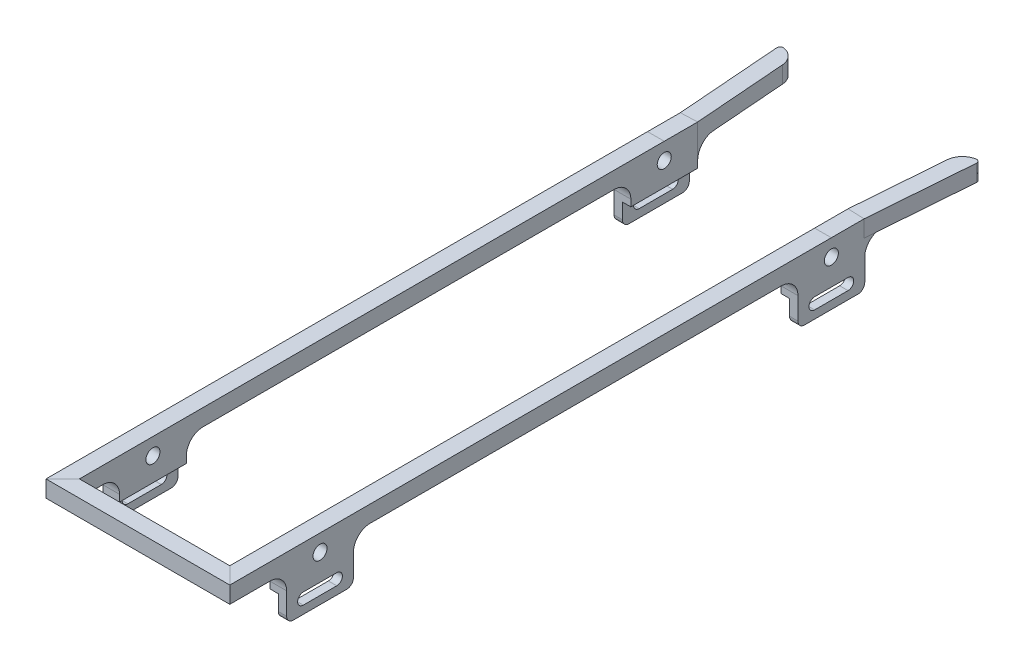
SolidWorks part; units mm, degrees
ref_plane "Front Plane" through (0, 0, 0) normal (0, 0, 1) x (1, 0, 0)
ref_plane "Top Plane" through (0, 0, 0) normal (0, 1, 0) x (1, 0, 0)
ref_plane "Right Plane" through (0, 0, 0) normal (1, 0, 0) x (0, 0, -1)
sketch "rail_path" plane through (0, 0, 0) normal (0, 1, 0) x (1, 0, 0)
  line L0 (28.575, 111.125) -> (28.575, 123.825)
  line L1 (-28.575, -111.125) -> (28.575, -111.125)
  line L2 (-28.575, -111.125) -> (-28.575, 111.125)
  line L3 (-28.575, 111.125) -> (28.575, 111.125) construction
  line L4 (28.575, -111.125) -> (28.575, 111.125)
  line L5 (-28.575, -111.125) -> (28.575, 111.125) construction
  line L6 (-28.575, 111.125) -> (28.575, -111.125) construction
  line L7 (-28.575, 111.125) -> (-28.575, 123.825)
  line L8 (28.575, 123.825) -> (31.75, 165.1)
  line L9 (-28.575, 123.825) -> (-31.75, 165.1)
  point P0 (0, 0)
  dimension "D1" = 222.25
  dimension "D2" = 57.15
  dimension "D3" = 12.7
  dimension "D4" = 12.7
  dimension "D5" = 41.275
  dimension "D6" = 3.175
  dimension "D7" = 3.175
sketch "rail_profile" plane through (0, 0, 0) normal (0, 0, 1) x (1, 0, 0)
  line L0 (-28.575, 0) -> (28.575, 0) construction
  line L1 (28.575, 0) -> (34.925, 0)
  line L2 (28.575, 0) -> (28.575, 6.35)
  line L3 (28.575, 6.35) -> (34.925, 6.35)
  line L4 (34.925, 0) -> (34.925, 6.35)
  line L5 (-28.575, 0) -> (28.575, 0) construction
  dimension "D1" = 6.35
  dimension "D2" = 6.35
sweep "Sweep1" add profiles "rail_profile" path "rail_path"
sketch "clip_profile" plane through (0, 0, 0) normal (0, 0, 1) x (1, 0, 0)
  line L4 (28.575, 0) -> (-28.575, 0)
  line L12 (-28.575, 6.35) -> (28.575, 6.35)
  line L34 (34.925, -17.272) -> (31.75, -17.272)
  line L38 (28.575, -8.89) -> (31.75, -8.89)
  line L39 (31.75, -17.272) -> (31.75, -8.89)
  line L47 (31.75, 6.35) -> (38.0813, 6.35)
  line L48 (34.925, -17.272) -> (34.925, -8.89)
  line L49 (38.0813, 6.35) -> (38.0813, 0)
  line L50 (28.575, -8.89) -> (34.925, -8.89)
  line L51 (28.575, -8.89) -> (28.575, 0)
  line L52 (28.575, 0) -> (34.925, 0)
  line L53 (34.925, -8.89) -> (34.925, 0)
  line L54 (31.75, 6.35) -> (38.0813, 6.35)
  line L55 (38.0813, 6.35) -> (38.0813, 0)
  line L56 (38.0813, 0) -> (31.75, 0)
  line L57 (31.75, 0) -> (28.575, 0)
  line L58 (38.0813, 0) -> (31.75, 0)
  line L59 (-28.575, 0) -> (-31.75, 0)
  line L60 (-31.75, 0) -> (-38.0813, 0)
  line L61 (-38.0813, 0) -> (-38.0813, 6.35)
  line L62 (-38.0813, 6.35) -> (-31.75, 6.35)
  line L63 (-31.75, 6.35) -> (-28.575, 6.35)
  line L64 (31.75, 0) -> (28.575, 0)
  line L65 (28.575, 6.35) -> (31.75, 6.35)
  line L66 (-28.575, 0) -> (-31.75, 0)
  line L67 (-31.75, 0) -> (-38.0813, 0)
  line L68 (-38.0813, 0) -> (-38.0813, 6.35)
  line L69 (-38.0813, 6.35) -> (-31.75, 6.35)
  line L70 (-31.75, 6.35) -> (-28.575, 6.35)
  line L71 (28.575, 6.35) -> (31.75, 6.35)
  dimension "D1" = 8.89
  dimension "D2" = 3.175
  dimension "D4" = 8.382
ref_plane "BackClipPlane" through (0, 0, 83.185) normal (0, 0, -1) x (-1, 0, 0)
ref_plane "FrontClipPlane" through (0, 0, -111.125) normal (0, 0, -1) x (-1, 0, 0)
sketch "BackClipProfile" plane through (0, 0, 83.185) normal (0, 0, -1) x (-1, 0, 0)
  line L24 (-34.925, -8.89) -> (-34.925, 0) construction
  line L25 (-34.925, -17.272) -> (-34.925, -8.89) construction
  line L26 (-34.925, -17.272) -> (-31.75, -17.272) construction
  line L27 (-31.75, -17.272) -> (-31.75, -8.89) construction
  line L28 (-28.575, -8.89) -> (-31.75, -8.89) construction
  line L29 (-28.575, -8.89) -> (-28.575, 0) construction
  line L30 (-34.925, -8.89) -> (-34.925, 0)
  line L31 (-34.925, -17.272) -> (-34.925, -8.89)
  line L32 (-34.925, -17.272) -> (-31.75, -17.272)
  line L33 (-31.75, -17.272) -> (-31.75, -8.89)
  line L34 (-28.575, -8.89) -> (-31.75, -8.89)
  line L35 (-28.575, -8.89) -> (-28.575, 0)
  line L36 (-28.575, 0) -> (-34.925, 0)
sketch "FrontClipProfile" plane through (0, 0, -111.125) normal (0, 0, -1) x (-1, 0, 0)
  line L24 (-31.75, -17.272) -> (-31.75, -8.89) construction
  line L25 (-34.925, -17.272) -> (-31.75, -17.272) construction
  line L26 (-34.925, -17.272) -> (-34.925, -8.89) construction
  line L27 (-34.925, -8.89) -> (-34.925, 0) construction
  line L28 (-28.575, -8.89) -> (-31.75, -8.89) construction
  line L29 (-28.575, -8.89) -> (-28.575, 0) construction
  line L30 (-31.75, -17.272) -> (-31.75, -8.89)
  line L31 (-34.925, -17.272) -> (-31.75, -17.272)
  line L32 (-34.925, -17.272) -> (-34.925, -8.89)
  line L33 (-34.925, -8.89) -> (-34.925, 0)
  line L34 (-28.575, -8.89) -> (-31.75, -8.89)
  line L35 (-28.575, -8.89) -> (-28.575, 0)
  line L36 (-28.575, 0) -> (-34.925, 0)
extrude "BackClip" add sketch "BackClipProfile" along normal mid plane 25.4
mirror "BackClipMirror" about plane through (0, 0, 0) normal (1, 0, 0) of "BackClip"
extrude "FrontClip" add sketch "FrontClipProfile" along normal mid plane 25.4
mirror "FrontClipMirror" about plane through (0, 0, 0) normal (1, 0, 0) of "FrontClip"
sketch "Sketch8" plane through (28.575, 0, 0) normal (-1, 0, 0) x (0, 0, 1)
  line L0 (83.185, 3.4925) -> (83.185, -3.4925) construction
  line L9 (111.125, 6.35) -> (-111.125, 6.35) construction
  line L17 (111.125, 6.35) -> (-111.125, 6.35) construction
  circle A2 centre (83.185, 0) radius 2.667
  dimension "D2" = 5.334
extrude "Cut-Extrude1" cut sketch "Sketch8" against normal through all both and the other way through all
ref_plane "Plane1" through (0, 0, -13.97) normal (0, 0, -1) x (-1, 0, 0)
sketch "Sketch10" plane through (31.75, 0, 0) normal (-1, 0, 0) x (0, 0, 1)
  line L0 (76.835, -12.065) -> (89.535, -12.065) construction
  line L1 (76.835, -9.906) -> (89.535, -9.906)
  line L2 (76.835, -14.224) -> (89.535, -14.224)
  line L3 (70.485, -8.89) -> (95.885, -8.89) construction
  line L4 (83.185, 3.4925) -> (83.185, -3.4925) construction
  arc A0 (76.835, -9.906) -> (76.835, -14.224) centre (76.835, -12.065) ccw
  arc A1 (89.535, -14.224) -> (89.535, -9.906) centre (89.535, -12.065) ccw
  point P2 (83.185, -12.065)
  dimension "D2" = 2.159
  dimension "D1" = 3.175
  dimension "D3" = 12.7
fillet "Fillet1" radius 2.54 8 edges at (-33.3375, -17.272, -123.825) (-33.3375, -17.272, -98.425) (-33.3375, -17.272, 70.485) (-33.3375, -17.272, 95.885) (33.3375, -17.272, 70.485) (33.3375, -17.272, 95.885) (33.3375, -17.272, -98.425) (33.3375, -17.272, -123.825)
mirror "Mirror2" about plane through (0, 0, -13.97) normal (0, 0, -1) of "Cut-Extrude1"
extrude "Cut-Extrude3" cut sketch "Sketch10" against normal through all both and the other way through all
mirror "Mirror3" about plane through (0, 0, -13.97) normal (0, 0, -1) of "Cut-Extrude3"
fillet "Fillet3" radius 6.35 2 edges at (31.75, 3.175, -165.1) (-31.75, 3.175, -165.1)
fillet "Fillet5" radius 1.27 2 edges at (38.0813, 3.175, -164.613) (-38.0813, 3.175, -164.613)
fillet "Fillet10" radius 6.35 8 edges at (-31.75, 0, 70.485) (-31.75, 0, 95.885) (31.75, 0, 95.885) (31.75, 0, 70.485) (31.75, 0, -98.425) (-31.75, 0, -98.425) (31.75, 0, -123.825) (-31.75, 0, -123.825)
equation "\"rail_horizontal_clearance\"= 0.25 / 2"
